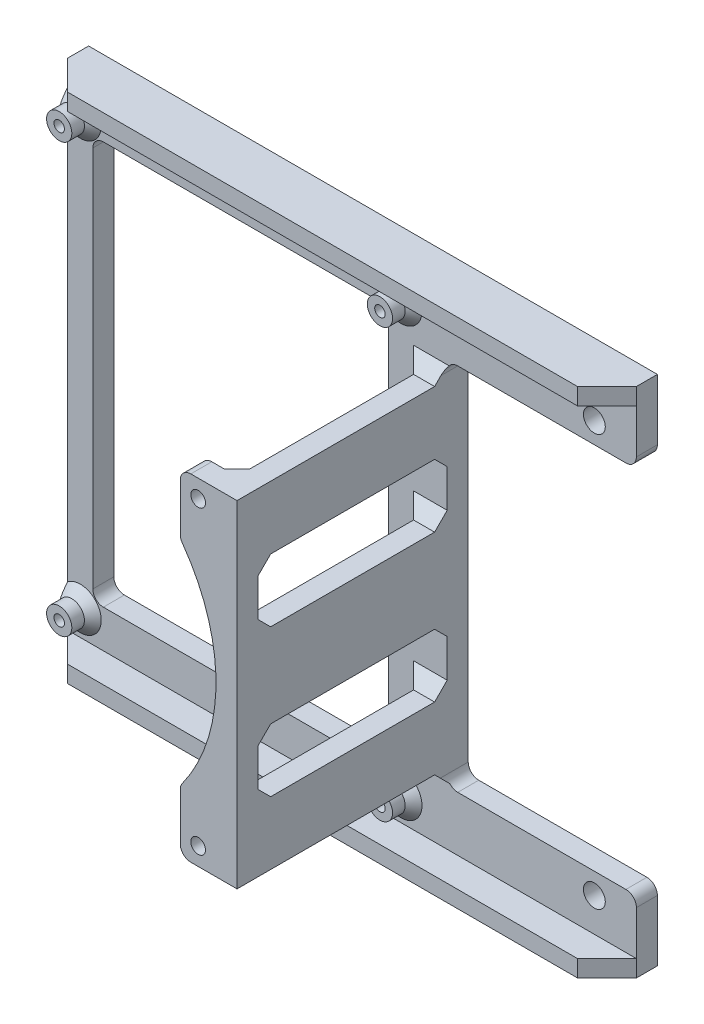
SolidWorks part; units mm, degrees
ref_plane "Спереди" through (0, 0, 0) normal (0, 0, 1) x (1, 0, 0)
ref_plane "Сверху" through (0, 0, 0) normal (0, 1, 0) x (1, 0, 0)
ref_plane "Справа" through (0, 0, 0) normal (1, 0, 0) x (0, 0, -1)
sketch "Эскиз1" plane through (0, 0, 0) normal (0, 0, 1) x (1, 0, 0)
  line L0 (35.15, 47.925) -> (35.15, -47.925)
  line L4 (41.15, 53.925) -> (-41.15, 53.925)
  line L5 (41.15, 53.925) -> (41.15, -53.925)
  line L6 (41.15, -53.925) -> (-41.15, -53.925)
  line L7 (-41.15, 53.925) -> (-41.15, -53.925)
  line L8 (35.15, -47.925) -> (-35.15, -47.925)
  line L9 (-35.15, 47.925) -> (-35.15, -47.925)
  line L10 (35.15, 47.925) -> (-35.15, 47.925)
  line L11 (41.15, 53.925) -> (-41.15, -53.925) construction
  point P0 (0, 0)
  dimension "D1" = 6
  dimension "D7" = 107.85
  dimension "D8" = 82.3
extrude "Бобышка-Вытянуть1" add sketch "Эскиз1" along normal blind 5
sketch "Эскиз2" plane through (0, 0, 5) normal (0, 0, 1) x (1, 0, 0)
  line L0 (41.15, 53.925) -> (-41.15, 53.925) construction
  line L1 (41.15, -53.925) -> (41.15, 53.925) construction
  line L2 (-41.15, 53.925) -> (41.15, -53.925) construction
  line L3 (0, 0) -> (50.2481, 0) construction
  line L4 (0, -53.925) -> (0, -50053.925) construction
  circle A1 centre (38.15, 50.925) radius 3
  circle A2 centre (38.15, -50.925) radius 3
  circle A3 centre (-38.15, -50.925) radius 3
  circle A4 centre (-38.15, 50.925) radius 3
  point P15 (0, 0)
  dimension "D2" = 6
extrude "Бобышка-Вытянуть2" add sketch "Эскиз2" along normal blind 5
sketch "Эскиз3" plane through (0, 0, 10) normal (0, 0, 1) x (1, 0, 0)
  circle A3 centre (38.15, 50.925) radius 1.25
  circle A4 centre (38.15, -50.925) radius 1.25
  circle A5 centre (-38.15, 50.925) radius 1.25
  circle A6 centre (-38.15, -50.925) radius 1.25
  dimension "D1" = 2.5
  dimension "D2" = 2.5
  dimension "D3" = 2.5
  dimension "D4" = 2.5
extrude "Вырез-Вытянуть1" cut sketch "Эскиз3" against normal through all
sketch "Эскиз4" plane through (0, 0, 0) normal (0, 0, -1) x (-1, 0, 0)
  line L1 (-41.15, 53.925) -> (-94.15, 53.925)
  line L2 (-41.15, 53.925) -> (-41.15, 43.925)
  line L3 (-41.15, 43.925) -> (-94.15, 43.925)
  line L4 (-94.15, 53.925) -> (-94.15, 43.925)
  circle A0 centre (-38.15, 50.925) radius 1.25 construction
  dimension "D3" = 56
  dimension "D1" = 10
extrude "Бобышка-Вытянуть3" add sketch "Эскиз4" against normal up to surface (5 mm away) up to face at (0, 0, 5)
sketch "Эскиз6" plane through (0, 0, 5) normal (0, 0, 1) x (1, 0, 0)
  line L0 (94.15, 43.925) -> (94.15, 53.925) construction
  line L1 (94.15, 53.925) -> (38.15, 53.925) construction
  circle A0 centre (84.15, 48.925) radius 2.6
  dimension "D1" = 5.2
  dimension "D2" = 10
  dimension "D3" = 5
extrude "Вырез-Вытянуть2" cut sketch "Эскиз6" against normal through all and the other way through all
ref_plane "Плоскость1" through (0, 8.925, 0) normal (0, 1, 0) x (1, 0, 0)
sketch "Эскиз14" plane through (94.15, 0, 0) normal (1, 0, 0) x (0, 0, -1)
  line L0 (0, 53.925) -> (0, 60.925)
  line L1 (0, 60.925) -> (-12, 60.925)
  line L2 (-12, 60.925) -> (-12, 56.925)
  line L3 (-12, 56.925) -> (-5, 56.925)
  line L4 (-5, 56.925) -> (-5, 53.925)
  line L6 (-5, 53.925) -> (0, 53.925)
  dimension "D1" = 3
  dimension "D2" = 4
  dimension "D3" = 12
extrude "Бобышка-Вытянуть9" add sketch "Эскиз14" against normal up to surface (135.3 mm away) up to face at (-41.15, 0, 3.3333)
mirror "Зеркальное отражение1" about plane through (0, 0, 0) normal (0, 1, 0) of "Бобышка-Вытянуть9", "Вырез-Вытянуть2", "Бобышка-Вытянуть3"
sketch "Эскиз9" plane through (0, 43.925, 0) normal (0, 1, 0) x (1, 0, 0)
  line L0 (41.15, 0) -> (49.15, 0)
  line L1 (49.15, 0) -> (49.15, -55)
  line L2 (49.15, -55) -> (44.15, -55)
  line L5 (44.15, -55) -> (44.15, -5)
  line L6 (44.15, -5) -> (41.15, -5)
  line L7 (41.15, -5) -> (41.15, 0)
  dimension "D1" = 5
  dimension "D3" = 3
  dimension "D5" = 55
extrude "Бобышка-Вытянуть6" add sketch "Эскиз9" against normal blind 80 from offset 4 offset against normal yes
sketch "Эскиз15" plane through (0, 43.925, 0) normal (0, -1, 0) x (1, 0, 0)
  line L1 (49.15, 0) -> (41.15, 0)
  line L2 (49.15, 0) -> (49.15, 5)
  line L3 (49.15, 5) -> (41.15, 5)
  line L4 (41.15, 0) -> (41.15, 5)
extrude "Бобышка-Вытянуть10" add sketch "Эскиз15" along normal up to surface (87.85 mm away) up to face at (67.65, -43.925, 2.5)
sketch "Эскиз10" plane through (0, 0, 55) normal (0, 0, 1) x (1, 0, 0)
  line L0 (44.15, -40.075) -> (44.15, 39.925) construction
  line L1 (35.65, 39.925) -> (49.15, 39.925)
  line L2 (49.15, 39.925) -> (49.15, -40.075)
  line L3 (49.15, -40.075) -> (35.65, -40.075)
  line L4 (49.15, -40.075) -> (49.15, 39.925) construction
  line L5 (35.65, 39.925) -> (35.65, 25.3415)
  line L6 (35.65, -25.4915) -> (35.65, -40.075)
  arc A0 (35.65, -25.4915) -> (35.65, 25.3415) centre (1.9, -0.075) ccw
  point P5 (44.15, -0.075)
  point P6 (49.15, -0.075)
  dimension "D1" = 84.5
  dimension "D2" = 80
  dimension "D3" = 13.5
extrude "Бобышка-Вытянуть7" add sketch "Эскиз10" against normal blind 5
sketch "Эскиз11" plane through (0, 0, 55) normal (0, 0, 1) x (1, 0, 0)
  line L0 (49.15, 39.925) -> (35.65, 39.925) construction
  line L1 (49.15, -40.075) -> (49.15, 39.925) construction
  line L2 (35.65, -40.075) -> (49.15, -40.075) construction
  circle A0 centre (39.9, 35.675) radius 1.75
  circle A1 centre (39.9, -35.825) radius 1.75
  dimension "D1" = 3.5
  dimension "D2" = 3.5
  dimension "D4" = 9.25
  dimension "D5" = 4.25
  dimension "D3" = 4.25
extrude "Вырез-Вытянуть3" cut sketch "Эскиз11" against normal up to surface (5 mm away) up to face at (40.4172, 26.4521, 50)
sketch "Эскиз16" plane through (49.15, 0, 0) normal (1, 0, 0) x (0, 0, -1)
  line L0 (-5, -40.075) -> (-5, 39.925) construction
  line L1 (-50, -25.075) -> (-5, -25.075)
  line L2 (-50, -25.075) -> (-50, -10.075)
  line L3 (-50, -10.075) -> (-5, -10.075)
  line L4 (-5, -25.075) -> (-5, -10.075)
  line L5 (-50, 9.925) -> (-5, 9.925)
  line L6 (-50, 9.925) -> (-50, 24.925)
  line L7 (-50, 24.925) -> (-5, 24.925)
  line L8 (-5, 9.925) -> (-5, 24.925)
  line L9 (-50, -40.075) -> (-50, -0.075) construction
  line L10 (-55, -40.075) -> (-5, -40.075) construction
  line L11 (-55, 39.925) -> (-5, 39.925) construction
  dimension "D1" = 15
  dimension "D2" = 15
  dimension "D3" = 15
  dimension "D4" = 20
extrude "Вырез-Вытянуть4" cut sketch "Эскиз16" against normal through all
fillet "Скругление1" radius 2.5 12 edges at (94.15, -43.925, 2.5) (94.15, 43.925, 2.5) (-35.15, 47.925, 2.5) (-35.15, -47.925, 2.5) (35.15, -47.925, 2.5) (35.15, 47.925, 2.5) (35.65, 25.3415, 52.5) (35.65, -25.4915, 52.5) (35.65, -40.075, 52.5) (35.65, 39.925, 52.5) (49.15, -43.925, 2.5) (49.15, 43.925, 2.5)
chamfer "Фаска1" distance 2 angle 45 4 edges at (41.15, 50.925, 5) (-41.15, 50.925, 5) (-35.15, -50.925, 5) (35.15, -50.925, 5)
chamfer "Фаска2" distance 3 angle 45 15 edges at (44.15, -32.575, 5) (44.15, 32.425, 5) (46.65, -40.075, 5) (46.65, 39.925, 5) (46.65, -10.075, 5) (46.65, 9.925, 5) (44.15, -0.075, 5) (46.65, 24.925, 5) (46.65, -25.075, 5) (44.15, -32.575, 50) (46.65, -25.075, 50) (46.65, -10.075, 50) (46.65, 9.925, 50) (44.15, 32.425, 50) (46.65, 24.925, 50)
chamfer "Фаска3" distance 7 angle 45 4 edges at (94.15, 58.925, 12) (94.15, -58.925, 12) (-41.15, -58.925, 12) (-41.15, 58.925, 12)
